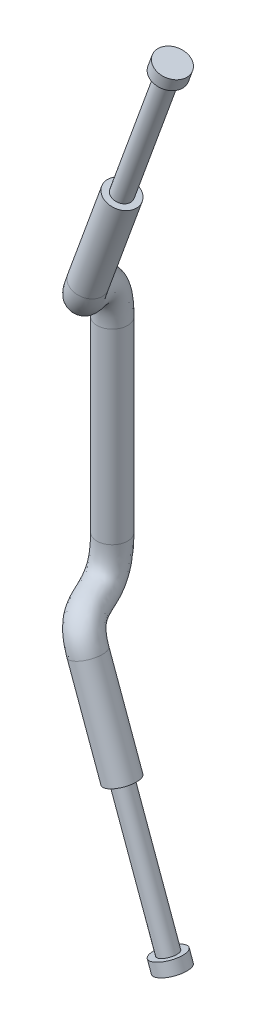
SolidWorks part; units mm, degrees
material "6061-T6 (SS)"
ref_plane "Front Plane" through (0, 0, 0) normal (1, 0, 0) x (0, 1, 0)
ref_plane "Top Plane" through (0, 0, 0) normal (0, 0, 1) x (0, 1, 0)
ref_plane "Right Plane" through (0, 0, 0) normal (0, 1, 0) x (-1, 0, 0)
sketch "Sketch1" plane through (0, 0, 0) normal (0, 0, 1) x (0, 1, 0)
  line L0 (-187.2211, 0) -> (66.2595, 0) construction
  line L1 (-75, 0) -> (-309.9232, -85.505) construction
  line L2 (75, 0) -> (114.4219, -14.3484) construction
  point P7 (-131.3816, -20.5212)
  point P8 (-309.9232, -85.505)
  point P9 (0, 0)
  point P10 (-75, 0)
  point P11 (91.844, -6.1307)
  point P12 (75, 0)
  point P14 (114.4219, -14.3484)
  dimension "D1" = 20
  dimension "D2" = 20
  dimension "D3" = 250
  dimension "D4" = 60
  dimension "D5" = 75
  dimension "D6" = 150
ref_plane "Plane1" through (85.505, -309.9232, 0) normal (0.342, -0.9397, 0) x (0.9397, 0.342, 0)
sketch "Sketch2" plane through (85.505, -309.9232, 0) normal (0.342, -0.9397, 0) x (0.9397, 0.342, 0)
  circle A0 centre (0, 0) radius 12.5
  circle A1 centre (0, 0) radius 7.5
  dimension "D1" = 25
  dimension "D2" = 15
extrude "Boss-Extrude1" add sketch "Sketch2" along normal blind 10 contours A0
extrude "Boss-Extrude2" add sketch "Sketch2<3>" against normal blind 110 contours A1
sketch "Sketch2<3>" plane through (85.505, -309.9232, 0) normal (0.342, -0.9397, 0) x (0.9397, 0.342, 0) same geometry as "Sketch2"
extrude "Boss-Extrude3" add sketch "Sketch2<4>" against normal blind 80 from surface contours A0 starting at face at (54.9305, -203.9918, 0)
sketch "Sketch2<4>" plane through (85.505, -309.9232, 0) normal (0.342, -0.9397, 0) x (0.9397, 0.342, 0) same geometry as "Sketch2"
sketch "Sketch3" plane through (0, 0, 0) normal (0, 1, 0) x (-1, 0, 0)
  circle A0 centre (0, -40) radius 12.5
  dimension "D1" = 25
  dimension "D2" = 40
mirror "Mirror1" about plane through (0, 0, 0) normal (0, 1, 0) of bodies 103
extrude "Boss-Extrude5" add sketch "Sketch3" along normal mid plane 150 separate body
sketch3d "3DSketch2"
  line L2 (20.5212, 131.3816, 0) -> (20.1792, 130.4419, 0)
  line L3 (20.5212, 131.3816, 0) -> (47.8828, 206.557, 0) construction
  line L4 (0, 75, -40) -> (0, 76, -40)
  line L5 (0, 75, -40) -> (0, -75, -40) construction
  line L6 (20.1792, 130.4419, 0) -> (20.5212, 131.3816, 0) construction
  line L8 (0, 75, 0) -> (14.3484, 114.4219, 0) construction
  spline S0 degree 3 poles (20.1792, 130.4419, 0) (7.2747, 94.9871, 0) (0, 128.7362, -40) (0, 76, -40) knots 0 0 0 0 1 1 1 1
  dimension "D1" = 1
  dimension "D2" = 1
sketch "Sketch7" plane through (44.6257, 122.6082, 0) normal (-0.342, -0.9397, 0) x (0.9397, -0.342, 0)
  circle A1 centre (-25.6515, 0) radius 12.5
  circle A2 centre (-25.6515, 0) radius 12.5
  dimension "D1" = 0
sweep "Sweep3" add profiles "Sketch7" path "3DSketch2"
mirror "Mirror2" about plane through (0, 0, 0) normal (0, 1, 0) of "Sweep3"
sketch "Sketch8" plane through (0, 0, 0) normal (0, 0, 1) x (0, 1, 0)
  line L1 (-400, 100) -> (0, 100)
  line L2 (-400, 100) -> (-400, -150)
  line L3 (-400, -150) -> (0, -150)
  line L4 (0, 100) -> (0, -150)
  dimension "D1" = 400
  dimension "D2" = 250
  dimension "D3" = 100
extrude "Cut-Extrude1" cut sketch "Sketch8" against normal through all both and the other way through all
mirror "Mirror3" about plane through (-100, 0, -53.9633) normal (0, 1, 0) of bodies 110
ref_plane "Plane2" through (0, 0, 0) normal (0, 0, -1) x (0.342, 0.9397, 0)
ref_plane "Plane3" through (-24.1045, 8.7733, 0) normal (0.9397, -0.342, 0) x (0.342, 0.9397, 0)
ref_plane "Plane4" through (-24.1045, -8.7733, 0) normal (-0.9397, -0.342, 0) x (0.342, -0.9397, 0)
ref_plane "Plane5" through (0, 0, 0) normal (0, 0, 1) x (0.342, -0.9397, 0)
